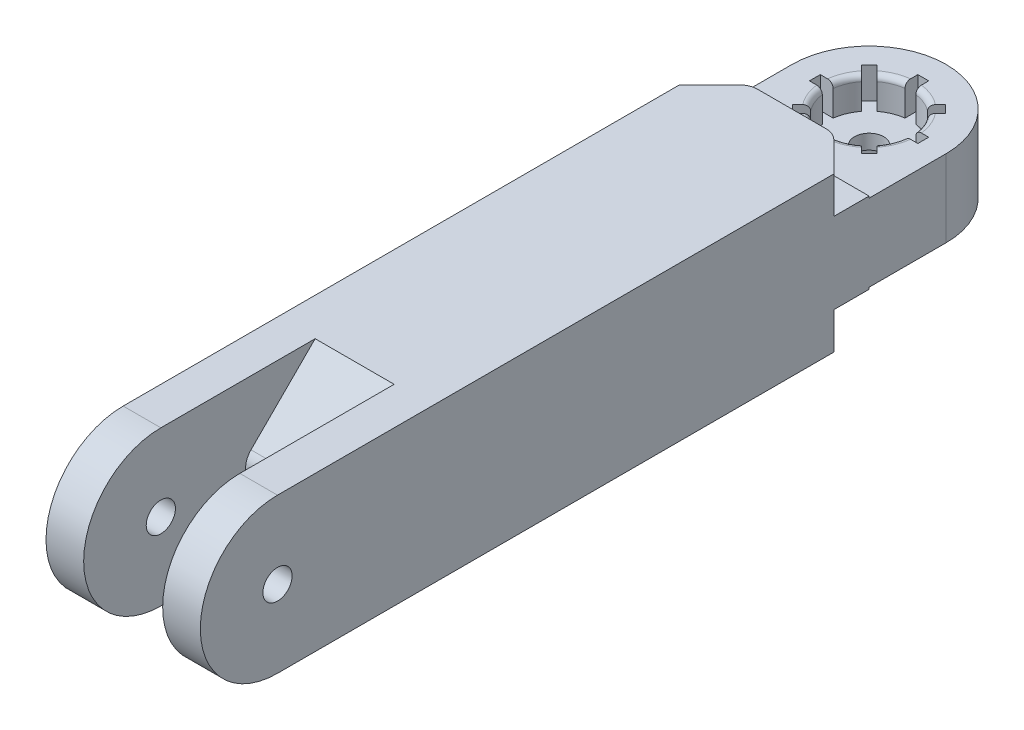
SolidWorks part; units mm, degrees
ref_plane "Front Plane" through (0, 0, 0) normal (0, 0, 1) x (1, 0, 0)
ref_plane "Top Plane" through (0, 0, 0) normal (0, 1, 0) x (1, 0, 0)
ref_plane "Right Plane" through (0, 0, 0) normal (1, 0, 0) x (0, 0, -1)
sketch "Sketch1" plane through (0, 0, 0) normal (0, 0, 1) x (1, 0, 0)
  line L1 (-21, 21) -> (21, 21)
  line L2 (-21, 21) -> (-21, -21)
  line L3 (-21, -21) -> (21, -21)
  line L4 (21, 21) -> (21, -21)
  line L5 (-21, 21) -> (21, -21) construction
  line L6 (-21, -21) -> (21, 21) construction
  point P0 (0, 0)
  dimension "D1" = 42
  dimension "D2" = 42
extrude "Boss-Extrude1" add sketch "Sketch1" along normal blind 140
ref_plane "Plane1" through (0, 0, 140) normal (0, 0, 1) x (1, 0, 0)
sketch "Sketch2" plane through (0, 0, 140) normal (0, 0, 1) x (1, 0, 0)
  line L0 (-21, -21) -> (21, -21) construction
  line L1 (-21, 21) -> (-10.75, 21)
  line L2 (-21, 21) -> (-21, -21)
  line L3 (-21, -21) -> (-10.75, -21)
  line L4 (-10.75, 21) -> (-10.75, -21)
  line L5 (21, 21) -> (-21, 21) construction
  line L6 (21, -21) -> (10.75, -21)
  line L7 (21, -21) -> (21, 21)
  line L8 (21, 21) -> (10.75, 21)
  line L9 (10.75, -21) -> (10.75, 21)
  dimension "D1" = 10.25
  dimension "D2" = 10.25
extrude "Boss-Extrude2" add sketch "Sketch2" along normal blind 21
ref_plane "Plane2" through (-10.75, 0, 0) normal (1, 0, 0) x (0, 0, -1)
sketch "Sketch3" plane through (-10.75, 0, 0) normal (1, 0, 0) x (0, 0, -1)
  line L0 (-161, -21) -> (-161, 21)
  arc A0 (-161, -21) -> (-161, 21) centre (-161, 0) cw
  dimension "D1" = 21
ref_plane "Plane3" through (0, -21, 0) normal (0, -1, 0) x (-1, 0, 0)
ref_plane "Plane4" through (10.75, 0, 0) normal (-1, 0, 0) x (0, 0, 1)
sketch "Sketch5" plane through (10.75, 0, 0) normal (-1, 0, 0) x (0, 0, 1)
  line L0 (161, 21) -> (161, -21)
  line L4 (140, 21) -> (140, -21)
  line L5 (140, -21) -> (161, -21)
  line L6 (161, -21) -> (161, 21)
  line L7 (161, 21) -> (140, 21)
  line L8 (140, 21) -> (140, -21)
  line L9 (140, -21) -> (161, -21)
  line L11 (161, 21) -> (140, 21)
  arc A0 (161, 21) -> (161, -21) centre (161, 0) cw
  dimension "D1" = 21
  dimension "D2" = 0
extrude "Boss-Extrude4" add sketch "Sketch5" against normal blind 10.25 contours A0 L0 region at (10.75, 0, 169.9127)
extrude "Boss-Extrude5" add sketch "Sketch3" against normal blind 10.25
sketch "Sketch6" plane through (10.75, 0, 0) normal (-1, 0, 0) x (0, 0, 1)
  line L0 (161, -21) -> (161, 21) construction
  circle A0 centre (161, 0) radius 3.975
  dimension "D1" = 7.95
extrude "Cut-Extrude1" cut sketch "Sketch6" against normal through all
ref_plane "Plane5" through (-10.75, 0, 0) normal (1, 0, 0) x (0, 0, -1)
sketch "Sketch8" plane through (-10.75, 0, 0) normal (1, 0, 0) x (0, 0, -1)
  line L0 (-161, -21) -> (-161, 21) construction
  circle A0 centre (-161, 0) radius 3.975
  dimension "D1" = 7.95
extrude "Cut-Extrude2" cut sketch "Sketch8" against normal through all
ref_plane "Plane6" through (0, 0, 0) normal (0, 0, -1) x (-1, 0, 0)
sketch "Sketch9" plane through (0, 0, 0) normal (0, 0, -1) x (-1, 0, 0)
  line L0 (21, 21) -> (21, -21) construction
  line L1 (21, 10.5) -> (-21, 10.5)
  line L2 (21, 10.5) -> (21, -10.5)
  line L3 (21, -10.5) -> (-21, -10.5)
  line L4 (-21, 10.5) -> (-21, -10.5)
  line L5 (-21, -21) -> (-21, 21) construction
  line L6 (-21, 21) -> (21, 21) construction
  line L7 (21, -21) -> (-21, -21) construction
  dimension "D1" = 10.5
  dimension "D2" = 10.5
extrude "Boss-Extrude6" add sketch "Sketch9" along normal blind 21
ref_plane "Plane7" through (0, -10.5, 0) normal (0, -1, 0) x (-1, 0, 0)
sketch "Sketch10" plane through (0, -10.5, 0) normal (0, -1, 0) x (-1, 0, 0)
  line L0 (-21, 21) -> (21, 21)
  arc A0 (-21, 21) -> (21, 21) centre (0, 21) cw
  dimension "D1" = 21
extrude "Boss-Extrude7" add sketch "Sketch10" against normal blind 21
sketch "Sketch11" plane through (0, -10.5, 0) normal (0, -1, 0) x (-1, 0, 0)
  line L0 (21, 21) -> (-21, 21) construction
  circle A0 centre (0, 21) radius 11.35
  dimension "D1" = 22.7
extrude "Cut-Extrude3" cut sketch "Sketch11" against normal blind 8.5
ref_plane "Plane8" through (10.75, 0, 0) normal (-1, 0, 0) x (0, 0, 1)
sketch "Sketch16" plane through (10.75, 0, 0) normal (-1, 0, 0) x (0, 0, 1)
  line L0 (140, 21) -> (140, 0)
  line L1 (140, 21) -> (140, -21) construction
  line L2 (140, 0) -> (140, -21)
  line L3 (140, -21) -> (119, -21)
  line L4 (119, -21) -> (140, 0)
  line L5 (140, 21) -> (119, 21)
  line L6 (119, 21) -> (140, 0)
  line L7 (161, 0) -> (140, 0) construction
  dimension "D1" = 21
  dimension "D2" = 21
extrude "Cut-Extrude4" cut sketch "Sketch16" along normal blind 21.5 contours L0 L5 L6 | L2 L3 L4
fillet "Fillet1" radius 5 1 edges at (0, 0, 140)
ref_plane "Plane9" through (0, -10.5, 0) normal (0, -1, 0) x (-1, 0, 0)
ref_plane "Plane10" through (0, 10.5, 0) normal (0, 1, 0) x (1, 0, 0)
sketch "Sketch18" plane through (0, 10.5, 0) normal (0, 1, 0) x (1, 0, 0)
  line L0 (21, 21) -> (-21, 21) construction
  circle A0 centre (0, 21) radius 11.35
  dimension "D1" = 22.7
extrude "Cut-Extrude5" cut sketch "Sketch18" against normal blind 8.5
sketch "Sketch19" plane through (0, -2, 0) normal (0, -1, 0) x (1, 0, 0)
  circle A0 centre (0, -21) radius 3.975
  dimension "D1" = 7.95
extrude "Cut-Extrude6" cut sketch "Sketch19" against normal blind 8.5
fillet "Fillet4" radius 1.5 1 edges at (11.35, -10.5, -21)
fillet "Fillet5" radius 1.5 1 edges at (-11.35, 10.5, -21)
sketch "Sketch20" plane through (0, 10.5, 0) normal (0, 1, 0) x (1, 0, 0)
  line L1 (-1.48, 35.755) -> (1.48, 35.755)
  line L2 (-1.48, 35.755) -> (-1.48, 31.945)
  line L3 (-1.48, 31.945) -> (1.48, 31.945)
  line L4 (1.48, 35.755) -> (1.48, 31.945)
  line L5 (-1.48, 35.755) -> (1.48, 31.945) construction
  line L6 (-1.48, 31.945) -> (1.48, 35.755) construction
  circle A0 centre (0, 21) radius 12.85 construction
  point P0 (0, 33.85)
  dimension "D1" = 2.96
  dimension "D2" = 3.81
extrude "Cut-Extrude7" cut sketch "Sketch20" against normal blind 8.5
pattern_circular "CirPattern1" count 8 over 360 about axis through (0, 2, -21) along (0, 1, 0) of "Cut-Extrude7"
ref_plane "Plane11" through (0, 0, 0) normal (0, 1, 0) x (1, 0, 0)
mirror "Mirror1" about plane through (0, 0, 0) normal (0, 1, 0) of "CirPattern1"
sketch "Sketch25" plane through (0, -21, 0) normal (0, -1, 0) x (1, 0, 0)
  line L0 (0, 0) -> (0, 119) construction
  line L1 (-10.75, 119) -> (10.75, 119) construction
  line L2 (-11.3946, 0) -> (-21, 9.6054)
  line L3 (16.25, 61.8903) -> (-16.25, 61.8903)
  line L4 (16.25, 61.8903) -> (16.25, 11.8903)
  line L5 (16.25, 11.8903) -> (-16.25, 11.8903)
  line L6 (-16.25, 61.8903) -> (-16.25, 11.8903)
  line L7 (16.25, 61.8903) -> (-16.25, 11.8903) construction
  line L8 (16.25, 11.8903) -> (-16.25, 61.8903) construction
  line L9 (21, 0) -> (-21, 0) construction
  line L10 (-21, 161) -> (-21, 0) construction
  line L11 (11.3946, 0) -> (21, 9.6054)
  point P5 (0, 36.8903)
  line M10 (-21, 161) -> (-21, 0)
  line M11 (-21, 0) -> (21, 0)
  line M12 (21, 0) -> (21, 161)
  dimension "D1" = 32.5
  dimension "D2" = 50
extrude "Cut-Extrude11" cut sketch "Sketch25" against normal blind 32 contours L3 L6 L5 L4 region at (0, -21, 36.8903)
extrude "Cut-Extrude12" cut sketch "Sketch25<3>" against normal blind 10 contours L2 M11 M10 | L11 M11 M12 region at (-17.7982, -21, 3.2018) region at (17.7982, -21, 3.2018)
sketch "Sketch25<3>" plane through (0, -21, 0) normal (0, -1, 0) x (1, 0, 0) same geometry as "Sketch25"
mirror "Mirror3" about plane through (0, 0, 0) normal (0, 1, 0) of "Cut-Extrude12"
fillet "Fillet11" radius 5 4 edges at (-11.3946, 16, 0) (11.3946, 16, 0) (11.3946, -16, 0) (-11.3946, -16, 0)
